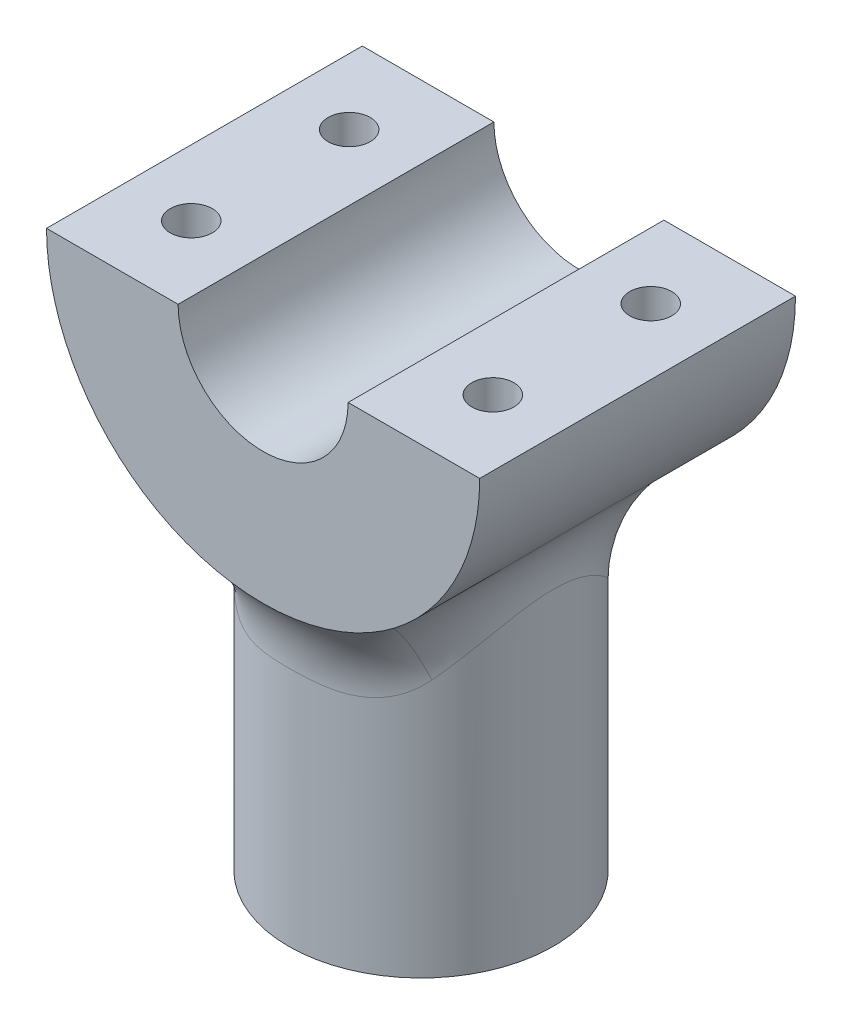
SolidWorks part; units mm, degrees
ref_plane "Front Plane" through (0, 0, 0) normal (0, 0, 1) x (1, 0, 0)
ref_plane "Top Plane" through (0, 0, 0) normal (0, 1, 0) x (1, 0, 0)
ref_plane "Right Plane" through (0, 0, 0) normal (1, 0, 0) x (0, 0, -1)
sketch "Sketch1" plane through (0, 0, 0) normal (0, 0, 1) x (1, 0, 0)
  line L0 (-8.075, 0) -> (-20.575, 0)
  line L3 (0, 0) -> (0, -8.075) construction
  line L5 (8.075, 0) -> (20.575, 0)
  arc A0 (-8.075, 0) -> (8.075, 0) centre (0, 0) ccw
  arc A1 (-20.575, 0) -> (20.575, 0) centre (0, 0) ccw
  dimension "D1" = 16.15
  dimension "D2" = 12.5
extrude "Boss-Extrude1" add sketch "Sketch1" along normal mid plane 30
sketch "Sketch2" plane through (0, 0, 0) normal (0, 1, 0) x (1, 0, 0)
  line L0 (-14.325, 15) -> (-14.325, -15) construction
  line L1 (-8.075, 15) -> (-20.575, 15) construction
  line L2 (-8.075, -15) -> (-20.575, -15) construction
  line L3 (-20.575, 0) -> (-8.075, 0) construction
  line L5 (-8.075, -15) -> (-8.075, 15) construction
  line L6 (-20.575, -15) -> (-20.575, 15) construction
  point P12 (-14.325, 7.5)
  point P13 (-14.325, -7.5)
  dimension "D1" = 7.5
hole_wizard "Ø4.0mm Dowel Hole1" positions "Sketch2" profile "Sketch3" hole size "Ø4.0" standard "ANSI Metric"
sketch "Sketch3" plane through (-14.325, 0, 7.5) normal (1, 0, 0) x (0, 0, 1)
  line L0 (0, 0) -> (0, 5)
  line L1 (0, 5) -> (2, 5)
  line L2 (2, 5) -> (2, 0)
  line L5 (2, 0) -> (0, 0)
  line L10 (0, 5) -> (-2, 5) construction
  line L11 (0, -6.35) -> (0, 107.95) construction
  dimension "Hole Dia." = 4
  dimension "Hole Depth" = 5
  dimension "Drill Angle" = 180
mirror "Mirror1" about plane through (0, 0, 0) normal (1, 0, 0) of "Ø4.0mm Dowel Hole1"
ref_plane "Plane1" through (0, -50, 0) normal (0, 1, 0) x (1, 0, 0)
sketch "Sketch4" plane through (0, -50, 0) normal (0, -1, 0) x (1, 0, 0)
  circle A0 centre (0, 0) radius 7.575
  circle A1 centre (0, 0) radius 12.575
  dimension "D1" = 15.15
  dimension "D2" = 5
extrude "Boss-Extrude3" add sketch "Sketch4" against normal up to next
fillet "Fillet2" radius 10 1 edges at (-3.2403, -20.3183, 12.1504)
